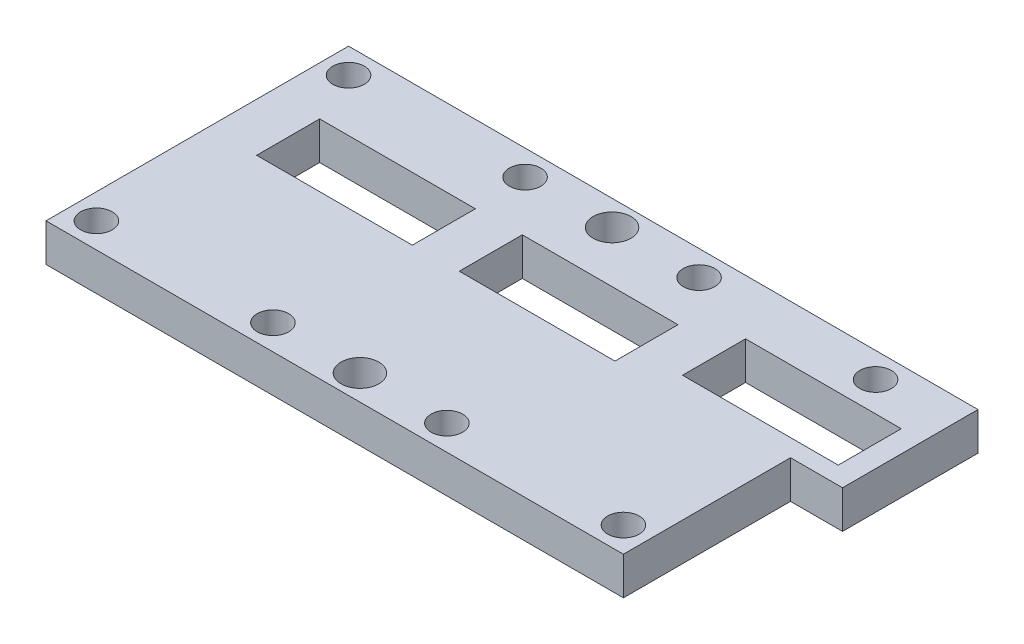
SolidWorks part; units mm, degrees
material "Plain Carbon Steel"
ref_plane "Front Plane" through (0, 0, 0) normal (0, 0, 1) x (1, 0, 0)
ref_plane "Top Plane" through (0, 0, 0) normal (0, 1, 0) x (1, 0, 0)
ref_plane "Right Plane" through (0, 0, 0) normal (1, 0, 0) x (0, 0, -1)
sketch "Sketch1" plane through (0, 0, 0) normal (0, 1, 0) x (1, 0, 0)
  line L0 (-229, 15.28) -> (-229, 9.28) construction
  line L1 (-229, -60) -> (0, -60)
  line L2 (-229, -60) -> (-229, 60)
  line L3 (-229, 60) -> (0, 60)
  line L4 (0, -60) -> (0, 60)
  point P0 (0, 0)
  dimension "D1" = 120
  dimension "D2" = 229
extrude "Boss-Extrude1" add sketch "Sketch1" against normal blind 15
sketch "Sketch2" plane through (0, 0, 0) normal (0, 1, 0) x (1, 0, 0)
  line L0 (21.6325, 5.27) -> (21.6325, 60) construction
  line L1 (0, 60) -> (20.6325, 60)
  line L2 (0, 60) -> (0, 6.27)
  line L3 (0, 6.27) -> (20.6325, 6.27)
  line L4 (20.6325, 60) -> (20.6325, 6.27)
  line L5 (1, 5.27) -> (21.6325, 5.27) construction
  dimension "D1" = 1
  dimension "D2" = 1
extrude "Boss-Extrude2" add sketch "Sketch2" against normal up to surface (15 mm away) up to face at (-114.5, -15, 0)
sketch "Sketch3" plane through (0, 0, 0) normal (0, 1, 0) x (1, 0, 0)
  line L0 (-48.75, 9.28) -> (-48.75, 26.191) construction
  line L1 (-49.75, 13.191) -> (12, 13.191)
  line L2 (-49.75, 13.191) -> (-49.75, 38.191)
  line L3 (-49.75, 38.191) -> (12, 38.191)
  line L4 (12, 13.191) -> (12, 38.191)
  line L5 (11, 27.5) -> (11, 9.28) construction
  line L7 (-29.25, 28.191) -> (-48.75, 28.191) construction
  dimension "D1" = 1
  dimension "D2" = 1
  dimension "D3" = 25
  dimension "D4" = 10
extrude "Cut-Extrude1" cut sketch "Sketch3" against normal up to next
sketch "Sketch4" plane through (0, 0, 0) normal (0, 1, 0) x (1, 0, 0)
  line L0 (-69, 15.28) -> (-69, 9.28) construction
  line L1 (-129.75, 29.6524) -> (-68, 29.6524)
  line L2 (-129.75, 29.6524) -> (-129.75, 4.6524)
  line L3 (-129.75, 4.6524) -> (-68, 4.6524)
  line L4 (-68, 29.6524) -> (-68, 4.6524)
  line L5 (-128.75, 9.28) -> (-128.75, 15.28) construction
  line L6 (-109.25, 19.6524) -> (-128.75, 19.6524) construction
  dimension "D1" = 1
  dimension "D2" = 1
  dimension "D3" = 10
  dimension "D4" = 25
extrude "Cut-Extrude2" cut sketch "Sketch4" against normal up to next
sketch "Sketch5" plane through (0, 0, 0) normal (0, 1, 0) x (1, 0, 0)
  line L0 (-208.75, 9.28) -> (-208.75, 15.28) construction
  line L1 (-209.75, 29.28) -> (-148, 29.28)
  line L2 (-209.75, 29.28) -> (-209.75, 4.28)
  line L3 (-209.75, 4.28) -> (-148, 4.28)
  line L4 (-148, 29.28) -> (-148, 4.28)
  line L5 (-149, 15.28) -> (-149, 9.28) construction
  line L6 (-149, 19.28) -> (-168.75, 19.28) construction
  dimension "D1" = 1
  dimension "D2" = 1
  dimension "D3" = 10
  dimension "D4" = 25
extrude "Cut-Extrude3" cut sketch "Sketch5" against normal up to next
sketch "Sketch7" plane through (0, 0, 0) normal (0, 1, 0) x (1, 0, 0)
  circle A0 centre (-114.5, 50) radius 7.5 construction
  circle A1 centre (-114.5, -50) radius 7.5 construction
  circle A2 centre (-114.5, 50) radius 7.5
  circle A3 centre (-114.5, -50) radius 7.5
extrude "Cut-Extrude5" cut sketch "Sketch7" against normal up to next
sketch "Sketch14" plane through (0, 0, 0) normal (0, 1, 0) x (1, 0, 0)
  circle A0 centre (-10, 50) radius 6.25 construction
  circle A1 centre (-10, -50) radius 6.25 construction
  circle A2 centre (-219, -50) radius 6.25 construction
  circle A3 centre (-219, 50) radius 6.25 construction
  circle A4 centre (-10, 50) radius 6.25
  circle A5 centre (-10, -50) radius 6.25
  circle A6 centre (-219, -50) radius 6.25
  circle A7 centre (-219, 50) radius 6.25
  circle A16 centre (-80, -50) radius 6.25 construction
  circle A17 centre (-80, 50) radius 6.25 construction
  circle A18 centre (-149, 50) radius 6.25 construction
  circle A19 centre (-149, -50) radius 6.25 construction
  circle A20 centre (-80, -50) radius 6.25
  circle A21 centre (-80, 50) radius 6.25
  circle A22 centre (-149, 50) radius 6.25
  circle A23 centre (-149, -50) radius 6.25
extrude "Cut-Extrude7" cut sketch "Sketch14" against normal up to next
